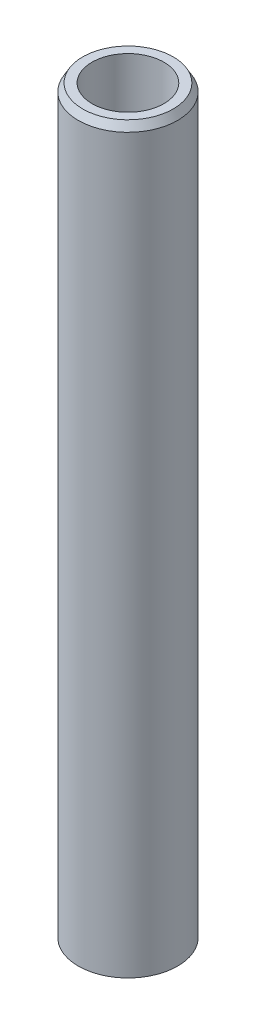
SolidWorks part; units mm, degrees
ref_plane "Front Plane" through (0, 0, 0) normal (0, 0, 1) x (1, 0, 0)
ref_plane "Top Plane" through (0, 0, 0) normal (0, 1, 0) x (1, 0, 0)
ref_plane "Right Plane" through (0, 0, 0) normal (1, 0, 0) x (0, 0, -1)
sketch "Sketch1" plane through (0, 0, 0) normal (0, 1, 0) x (1, 0, 0)
  circle A0 centre (0, 0) radius 15
  dimension "SHAFT_OD" = 30
extrude "Boss-Extrude1" add sketch "Sketch1" along normal blind 224.9186
sketch "Sketch2" plane through (0, 0, 0) normal (0, 1, 0) x (1, 0, 0)
  circle A0 centre (0, 0) radius 10.8663
  dimension "BORE_D" = 21.7326
extrude "Cut-Extrude1" cut sketch "Sketch2" along normal through all
chamfer "Chamfer1" distance 2.3242 angle 30 2 edges at (0, 224.9186, 15) (0, 0, 15) first distance on face at (0, 224.9186, 15) first distance on face at (0, 0, 10.8663)
